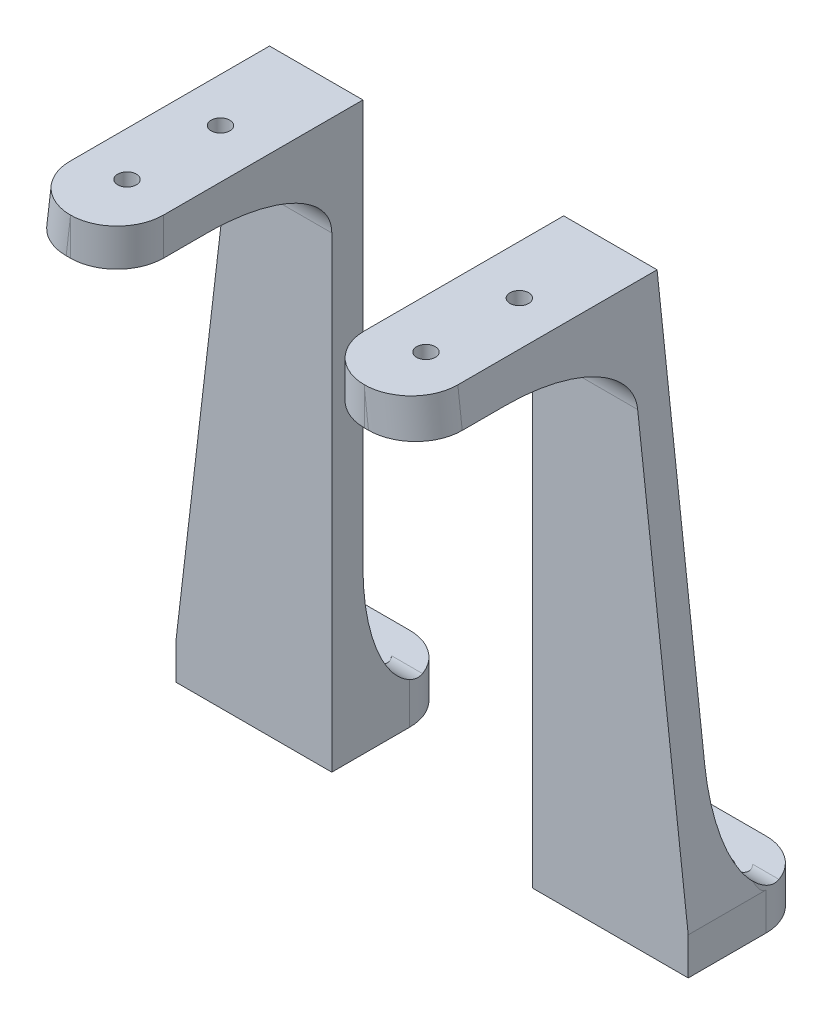
SolidWorks part; units mm, degrees
note: The reader was unsure of these and kept them because the rebuilt part matched: shared geometry of "Sketch3<3>", "Sketch5<3>".
ref_plane "Front Plane" through (0, 0, 0) normal (0, 0, 1) x (1, 0, 0)
ref_plane "Top Plane" through (0, 0, 0) normal (0, 1, 0) x (1, 0, 0)
ref_plane "Right Plane" through (0, 0, 0) normal (1, 0, 0) x (0, 0, -1)
sketch "Sketch2" plane through (0, 0, 0) normal (0, 0, 1) x (1, 0, 0)
  line L0 (-31.1207, 85) -> (-41.1207, 0)
  line L1 (-41.1207, 0) -> (-16.1207, 0)
  line L11 (-16.1207, 85) -> (-31.1207, 85)
  line L12 (-16.1207, 0) -> (-16.1207, 85)
  line L13 (0, -55) -> (0, 55) construction
  line L14 (41.1207, 0) -> (16.1207, 0)
  line L15 (31.1207, 85) -> (41.1207, 0)
  line L16 (16.1207, 85) -> (31.1207, 85)
  line L17 (16.1207, 0) -> (16.1207, 85)
  dimension "D1" = 16.1207
  dimension "D2" = 25
  dimension "D3" = 85
  dimension "D4" = 15
extrude "Stand" add sketch "Sketch2" along normal mid plane 5
sketch "Sketch3" plane through (0, 0, 0) normal (0, 0, 1) x (1, 0, 0)
  line L0 (-16.1207, 0) -> (-16.1207, 85) construction
  line L1 (-41.1207, 0) -> (-16.1207, 0)
  line L2 (-41.1207, 0) -> (-41.1207, -6)
  line L3 (-41.1207, -6) -> (-16.1207, -6)
  line L4 (-16.1207, 0) -> (-16.1207, -6)
  line L9 (-16.1207, 85) -> (-31.1207, 85) construction
  line L10 (-31.1207, 85) -> (-16.1207, 85)
  line L11 (-31.1207, 85) -> (-31.8266, 79)
  line L12 (-31.8266, 79) -> (-16.1207, 79)
  line L13 (-16.1207, 85) -> (-16.1207, 79)
  line L14 (-41.1207, 0) -> (-16.1207, 0) construction
  line L15 (-16.1207, 85) -> (-31.1207, 85) construction
  line L18 (-31.1207, 85) -> (-41.1207, 0) construction
  line L19 (0, -2.75) -> (0, 2.75) construction
  line L20 (41.1207, -6) -> (16.1207, -6)
  line L21 (16.1207, 0) -> (16.1207, -6)
  line L22 (41.1207, 0) -> (16.1207, 0)
  line L23 (41.1207, 0) -> (41.1207, -6)
  line L24 (16.1207, 85) -> (16.1207, 79)
  line L25 (31.1207, 85) -> (16.1207, 85)
  line L26 (31.1207, 85) -> (31.8266, 79)
  line L27 (31.8266, 79) -> (16.1207, 79)
  dimension "D1" = 6
  dimension "D2" = 6
  dimension "D3" = 25
  dimension "D4" = 15
extrude "Boss-Extrude2" add sketch "Sketch3" against normal blind 20 from surface at 2.5 contours L3 L4 L1 L2 | L20 L21 L22 L23 starting at face at (-26.1207, 42.5, 2.5)
extrude "Boss-Extrude3" add sketch "Sketch3<3>" along normal blind 37 contours L12 L13 L10 L11 | L24 L27 L26 L25
sketch "Sketch3<3>" plane through (0, 0, 0) normal (0, 0, 1) x (1, 0, 0) same geometry as "Sketch3"
sketch "Sketch4" plane through (0, 85, 0) normal (0, 1, 0) x (1, 0, 0)
  line L1 (0, -29.975) -> (0, 29.975) construction
  line L2 (-16.1207, 17.5) -> (-16.1207, 2.5) construction
  circle A0 centre (-24, 10) radius 1.5
  circle A1 centre (-24, -12.5) radius 1.5
  circle A2 centre (-34, 10) radius 1.5
  circle A3 centre (-24, -27.5) radius 1.5
  circle A4 centre (24, -27.5) radius 1.5
  circle A5 centre (34, 10) radius 1.5
  circle A6 centre (24, -12.5) radius 1.5
  circle A7 centre (24, 10) radius 1.5
  point P10 (0, 0)
  point P13 (-16.1207, 10)
  dimension "D1" = 3
  dimension "D2" = 24
  dimension "D3" = 22.5
  dimension "D4" = 10
  dimension "D5" = 15
  dimension "D6" = 24
extrude "ScrewHoles" cut sketch "Sketch4" against normal through all
fillet "Fillet3" radius 7.5 4 edges at (-16.1207, -3, -17.5) (-41.1207, -3, -17.5) (-16.1207, 82, 37) (-31.4736, 82, 37)
fillet "Fillet4" radius 20 1 edges at (-28.6207, 0, -2.5)
fillet "Fillet6" radius 20 1 edges at (-23.9736, 79, 2.5)
fillet "Fillet7" radius 7.5 4 edges at (16.1207, -3, -17.5) (41.1207, -3, -17.5) (31.4736, 82, 37) (16.1207, 82, 37)
fillet "Fillet8" radius 10 1 edges at (28.6207, 0, -2.5)
fillet "Fillet9" radius 10 1 edges at (23.9736, 79, 2.5)
sketch "Sketch5" plane through (0, 79, 0) normal (0, -1, 0) x (1, 0, 0)
  line L0 (0, -29.975) -> (0, 29.975) construction
  circle A0 centre (-24, -10) radius 3.5
  circle A2 centre (-24, 12.5) radius 3.5
  circle A4 centre (-34, -10) radius 3.5
  circle A5 centre (-34, 12.5) radius 3.5 [skipped]
  circle A6 centre (-24, 27.5) radius 3.5
  circle A7 centre (24, 27.5) radius 3.5
  circle A8 centre (34, -10) radius 3.5
  circle A9 centre (24, 12.5) radius 3.5
  circle A10 centre (24, -10) radius 3.5
  circle A11 centre (-24, 27.5) radius 1.5 construction
  point P22 (0, 0)
  dimension "D1" = 7
  dimension "D2" = 2
  dimension "D3" = 2
extrude "ScrewHoleClearance" cut sketch "Sketch5" along normal blind 40 contours A2 | A9 | A7 | A6
extrude "ScrewHoleClearance2" cut sketch "Sketch5<3>" against normal blind 40 from surface at 79 contours A4 | A0 | A10 | A8 starting at face at (-29.8707, 0, -15)
sketch "Sketch5<3>" plane through (0, 79, 0) normal (0, -1, 0) x (1, 0, 0) same geometry as "Sketch5"
equation "\"LegWide\"= 22.5"
